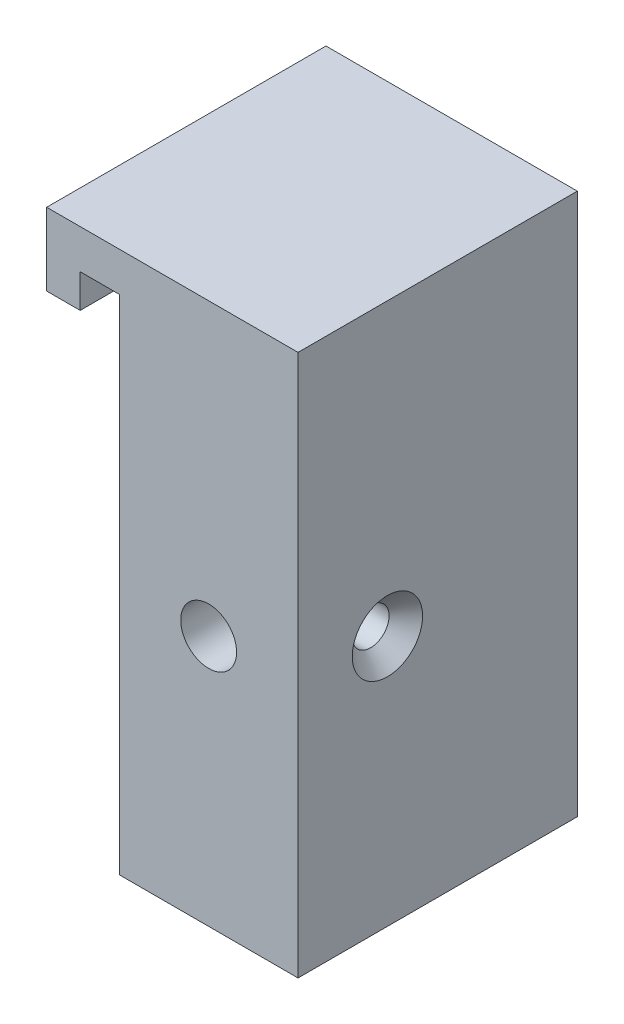
SolidWorks part; units mm, degrees
material "Stainless Steel (ferritic)"
ref_plane "Front Plane" through (0, 0, 0) normal (0, 0, 1) x (1, 0, 0)
ref_plane "Top Plane" through (0, 0, 0) normal (0, 1, 0) x (1, 0, 0)
ref_plane "Right Plane" through (0, 0, 0) normal (1, 0, 0) x (0, 0, -1)
sketch "Sketch1" plane through (0, 0, 0) normal (0, 0, 1) x (1, 0, 0)
  line L0 (0, 0) -> (0, 97)
  line L1 (0, 97) -> (-45, 97)
  line L2 (-45, 97) -> (-45, 84)
  line L3 (-45, 84) -> (-39, 84)
  line L4 (-39, 84) -> (-39, 90)
  line L5 (-39, 90) -> (-32, 90)
  line L6 (-32, 90) -> (-32, 0)
  line L7 (-32, 0) -> (0, 0)
  dimension "D1" = 97
  dimension "D2" = 32
  dimension "D3" = 45
  dimension "D4" = 6
  dimension "D5" = 13
  dimension "D6" = 7
extrude "Boss-Extrude1" add sketch "Sketch1" along normal mid plane 50
hole_wizard "Ø1.0mm Dowel Hole1" positions "Sketch2" profile "Sketch3" hole size "Ø1.0" standard "ANSI Metric"
sketch "Sketch2" plane through (0, 0, 25) normal (0, 0, 1) x (1, 0, 0)
  line L0 (-32, 0) -> (0, 0) construction
  line L1 (0, 0) -> (0, 97) construction
  point P0 (-16, 45)
  dimension "D1" = 45
  dimension "D2" = 16
sketch "Sketch3" plane through (-16, 45, 25) normal (1, 0, 0) x (0, -1, 0)
  line L0 (0, 0) -> (0, 25)
  line L1 (0, 25) -> (5, 25)
  line L2 (5, 25) -> (5, 0)
  line L5 (5, 0) -> (0, 0)
  line L10 (0, 25) -> (-5, 25) construction
  line L11 (0, -6.35) -> (0, 107.95) construction
  dimension "Hole Dia." = 10
  dimension "Hole Depth" = 25
  dimension "Drill Angle" = 180
hole_wizard "M8x1.0 Tapped Hole1" positions "Sketch4" profile "Sketch5" tap size "M8x1.0" standard "ANSI Metric"
sketch "Sketch4" plane through (0, 0, 0) normal (0, -1, 0) x (-1, 0, 0)
  line L0 (0, -25) -> (0, 25) construction
  point P0 (7, 0)
  point P2 (25, 0)
  dimension "D1" = 18
  dimension "D2" = 7
sketch "Sketch5" plane through (-7, 0, 0) normal (1, 0, 0) x (0, 0, -1)
  line L0 (0, 0) -> (0, 15)
  line L1 (0, 15) -> (3.5, 15)
  line L2 (3.5, 15) -> (3.5, 0)
  line L5 (3.5, 0) -> (0, 0)
  line L10 (0, 15) -> (-3.5, 15) construction
  line L11 (0, -6.35) -> (0, 107.95) construction
  dimension "Tap Drill Dia." = 7
  dimension "Tap Drill Depth" = 15
  dimension "Drill Angle" = 180
cosmetic thread "Hole Thread1" parameters "D1"=16, "D2"=8
cosmetic thread "Hole Thread2" parameters "D1"=16, "D2"=8
hole_wizard "CSK for M6 Flat Head Machine Screw1" positions "Sketch6" profile "Sketch7" countersink size "M6" standard "ANSI Metric" end condition up to next
sketch "Sketch6" plane through (0, 0, 0) normal (1, 0, 0) x (0, 0, -1)
  line L0 (-25, 0) -> (25, 0) construction
  line L1 (-25, 0) -> (-25, 97) construction
  point P0 (-9, 45)
  dimension "D1" = 45
  dimension "D2" = 16
sketch "Sketch7" plane through (0, 45, 9) normal (0, 1, 0) x (0, 0, -1)
  line L0 (0, 0) -> (0, 11)
  line L1 (0, 11) -> (3.3, 11)
  line L2 (3.3, 11) -> (3.3, 3)
  line L3 (3.3, 3) -> (6.3, 0)
  line L5 (6.3, 0) -> (0, 0)
  line L6 (-3.3, 3) -> (-6.3, 0) construction
  line L11 (0, -6.35) -> (0, 107.95) construction
  dimension "Thru Hole Dia." = 6.6
  dimension "Thru Hole Depth" = 11
  dimension "Near C'Sink Dia." = 12.6
  dimension "Near C'Sink Angle" = 90
